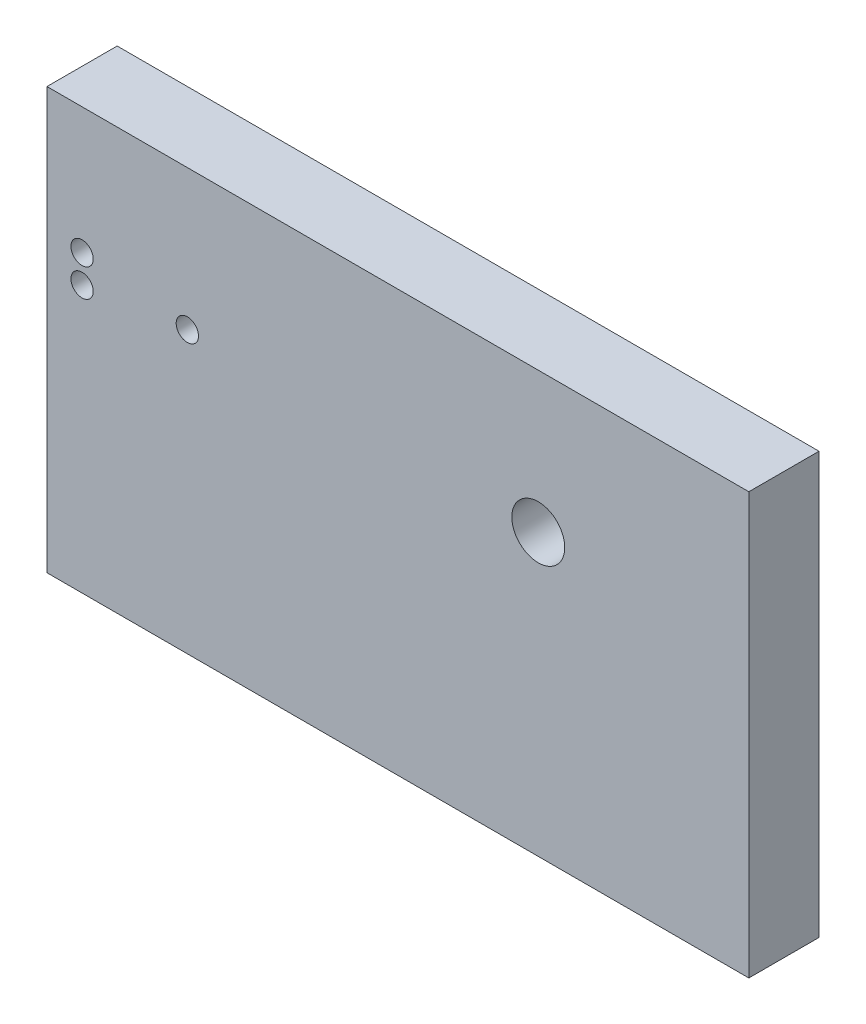
SolidWorks part; units mm, degrees
ref_plane "Front Plane" through (0, 0, 0) normal (0, 0, 1) x (1, 0, 0)
ref_plane "Top Plane" through (0, 0, 0) normal (0, 1, 0) x (1, 0, 0)
ref_plane "Right Plane" through (0, 0, 0) normal (1, 0, 0) x (0, 0, -1)
sketch "Sketch1" plane through (0, 0, 0) normal (0, 0, 1) x (1, 0, 0)
  line L1 (0, 0) -> (127, 0)
  line L2 (0, 0) -> (0, 76.2)
  line L3 (0, 76.2) -> (127, 76.2)
  line L4 (127, 0) -> (127, 76.2)
  dimension "D1" = 127
  dimension "D2" = 76.2
extrude "Boss-Extrude1" add sketch "Sketch1" along normal blind 12.7 contours L2 L1 L4 L3
hole_wizard "1/32 (0.159) Diameter Hole1" positions "Sketch5" profile "Sketch6" hole size "1/32" standard "ANSI Inch" end condition through all
sketch "Sketch5" plane through (0, 0, 12.7) normal (0, 0, 1) x (1, 0, 0)
  line L0 (0, 0) -> (0, 76.2) construction
  line L1 (0, 0) -> (127, 0) construction
  point P0 (25.4, 50.8)
  dimension "D1" = 25.4
  dimension "D2" = 50.8
sketch "Sketch6" plane through (25.4, 50.8, 12.7) normal (1, 0, 0) x (0, -1, 0)
  line L0 (0, 0) -> (0, 12.7)
  line L1 (0, 12.7) -> (2.0193, 12.7)
  line L2 (2.0193, 12.7) -> (2.0193, 0)
  line L5 (2.0193, 0) -> (0, 0)
  line L11 (0, -6.35) -> (0, 107.95) construction
  dimension "Thru Hole Dia." = 4.0386
  dimension "Thru Hole Depth" = 12.7
hole_wizard "#10-32 Tapped Hole1" positions "Sketch9" profile "Sketch10" tap size "#10-32" standard "ANSI Inch"
sketch "Sketch9" plane through (0, 0, 0) normal (0, -1, 0) x (-1, 0, 0)
  line L0 (0, -12.7) -> (-127, -12.7) construction
  line L1 (-19.05, -6.35) -> (-107.95, -6.35) construction
  line L3 (-63.5, -12.7) -> (-63.5, 0) construction
  line L4 (0, 0) -> (-127, 0) construction
  point P0 (-19.05, -6.35)
  point P2 (-107.95, -6.35)
  point P21 (-63.5, -6.35)
  dimension "D1" = 6.35
  dimension "D2" = 88.9
sketch "Sketch10" plane through (19.05, 0, 6.35) normal (1, 0, 0) x (0, 0, -1)
  line L0 (0, 0) -> (0, 13.9133)
  line L1 (0, 13.9133) -> (2.0193, 12.7)
  line L2 (2.0193, 12.7) -> (2.0193, 0)
  line L5 (2.0193, 0) -> (0, 0)
  line L10 (0, 13.9133) -> (-2.0193, 12.7) construction
  line L11 (0, -6.35) -> (0, 107.95) construction
  dimension "Tap Drill Dia." = 4.0386
  dimension "Tap Drill Depth" = 12.7
  dimension "Drill Angle" = 118
cosmetic thread "Hole Thread3" parameters "D1"=12.7, "D2"=4.826
cosmetic thread "Hole Thread4" parameters "D1"=12.7, "D2"=4.826
hole_wizard "V (0.377) Diameter Hole1" positions "Sketch14" profile "Sketch15" hole size "V" standard "ANSI Inch" end condition through all
sketch "Sketch14" plane through (0, 0, 12.7) normal (0, 0, 1) x (1, 0, 0)
  line L0 (0, 0) -> (127, 0) construction
  line L1 (0, 0) -> (0, 76.2) construction
  point P0 (88.9, 50.8)
  dimension "D1" = 50.8
  dimension "D2" = 88.9
sketch "Sketch15" plane through (88.9, 50.8, 12.7) normal (1, 0, 0) x (0, -1, 0)
  line L0 (0, 0) -> (0, 12.7)
  line L1 (0, 12.7) -> (4.7879, 12.7)
  line L2 (4.7879, 12.7) -> (4.7879, 0)
  line L5 (4.7879, 0) -> (0, 0)
  line L11 (0, -6.35) -> (0, 107.95) construction
  dimension "Thru Hole Dia." = 9.5758
  dimension "Thru Hole Depth" = 12.7
hole_wizard "#10-32 Tapped Hole2" positions "Sketch16" profile "Sketch17" tap size "#10-32" standard "ANSI Inch" end condition through all
sketch "Sketch16" plane through (0, 0, 12.7) normal (0, 0, 1) x (1, 0, 0)
  line L0 (0, 0) -> (0, 76.2) construction
  line L1 (0, 0) -> (127, 0) construction
  point P0 (6.35, 48.26)
  dimension "D1" = 6.35
  dimension "D2" = 48.26
cosmetic thread "Hole Thread5" parameters "D2"=4.826
sketch "Sketch17" plane through (6.35, 48.26, 12.7) normal (1, 0, 0) x (0, -1, 0)
  line L0 (0, 0) -> (0, 12.7)
  line L1 (0, 12.7) -> (2.0193, 12.7)
  line L2 (2.0193, 12.7) -> (2.0193, 0)
  line L5 (2.0193, 0) -> (0, 0)
  line L11 (0, -6.35) -> (0, 107.95) construction
  dimension "Thru Tap Drill Dia." = 4.0386
  dimension "Thru Tap Drill Depth" = 12.7
hole_wizard "#21 (0.159) Diameter Hole1" positions "Sketch18" profile "Sketch19" hole size "#21" standard "ANSI Inch" end condition through all
sketch "Sketch18" plane through (0, 0, 12.7) normal (0, 0, 1) x (1, 0, 0)
  line L0 (0, 0) -> (0, 76.2) construction
  line L1 (0, 0) -> (127, 0) construction
  point P0 (6.35, 53.34)
  dimension "D1" = 6.35
  dimension "D2" = 53.34
sketch "Sketch19" plane through (6.35, 53.34, 12.7) normal (1, 0, 0) x (0, -1, 0)
  line L0 (0, 0) -> (0, 12.7)
  line L1 (0, 12.7) -> (2.0193, 12.7)
  line L2 (2.0193, 12.7) -> (2.0193, 0)
  line L5 (2.0193, 0) -> (0, 0)
  line L11 (0, -6.35) -> (0, 107.95) construction
  dimension "Thru Hole Dia." = 4.0386
  dimension "Thru Hole Depth" = 12.7
